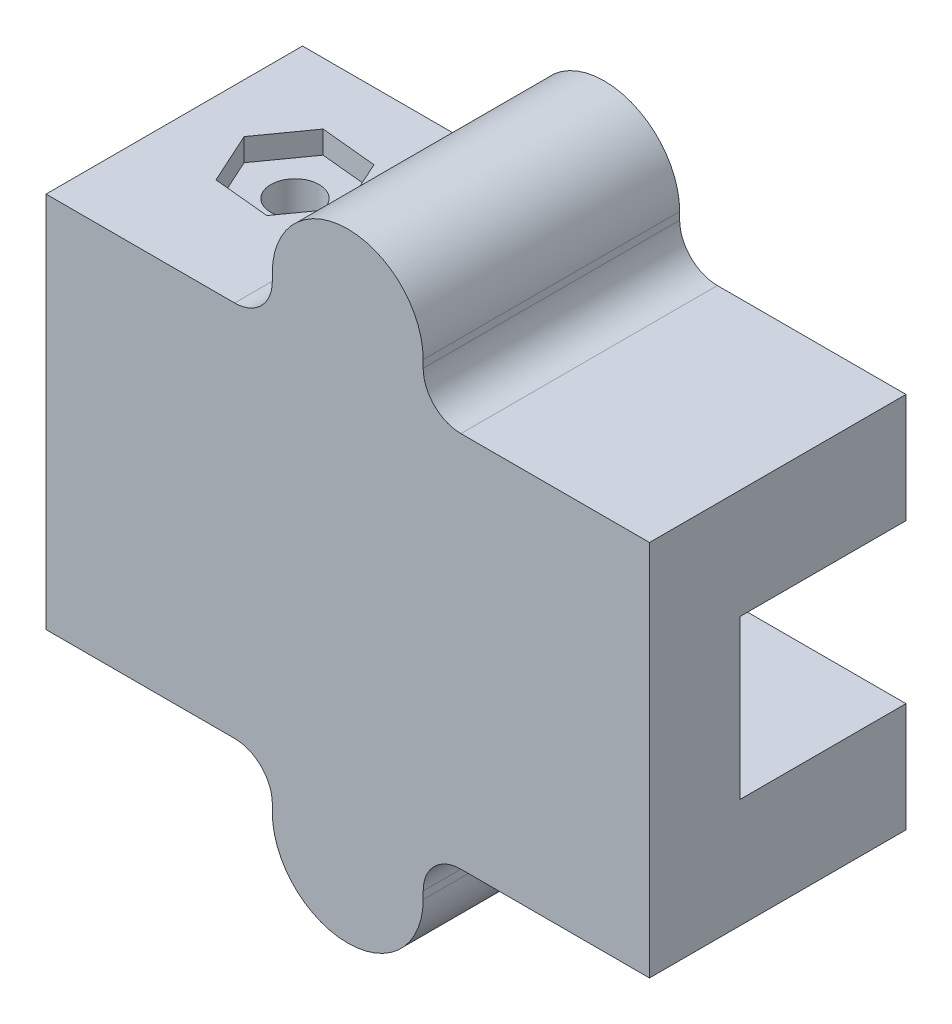
SolidWorks part; units mm, degrees
material "ABS"
ref_plane "Front Plane" through (0, 0, 0) normal (0, 0, 1) x (1, 0, 0)
ref_plane "Top Plane" through (0, 0, 0) normal (0, 1, 0) x (1, 0, 0)
ref_plane "Right Plane" through (0, 0, 0) normal (1, 0, 0) x (0, 0, -1)
sketch "Sketch1" plane through (0, 0, 0) normal (0, 0, 1) x (1, 0, 0)
  line L1 (0, 5.25) -> (0, -5.25) construction
  line L4 (-20, 12.5) -> (-7.5, 12.5)
  line L5 (20, -12.5) -> (20, 12.5)
  line L6 (-20, -12.5) -> (-7.5, -12.5)
  line L7 (-20, -12.5) -> (-20, 12.5)
  line L8 (-20, -5.25) -> (20, -5.25)
  line L9 (-20, -5.25) -> (20, -5.25) construction
  line L10 (-20, 5.25) -> (20, 5.25)
  line L11 (-20, 5.25) -> (20, 5.25) construction
  line L12 (-5, 15.5) -> (-5, 15)
  line L13 (5, 15.5) -> (5, 15)
  line L14 (7.5, 12.5) -> (20, 12.5)
  line L15 (-20, 12.5) -> (20, 12.5) construction
  line L17 (-20, 0) -> (20, 0) construction
  line L18 (7.5, -12.5) -> (20, -12.5)
  line L19 (-20, -12.5) -> (20, -12.5) construction
  line L20 (-5, -15) -> (-5, -15.5)
  line L21 (5, -15) -> (5, -15.5)
  circle A0 centre (0, 15.5) radius 2.4
  arc A1 (5, 15.5) -> (-5, 15.5) centre (0, 15.5) ccw
  arc A2 (5, 15) -> (7.5, 12.5) centre (7.5, 15) ccw
  arc A3 (-5, 15) -> (-7.5, 12.5) centre (-7.5, 15) cw
  arc A4 (5, -15) -> (7.5, -12.5) centre (7.5, -15) cw
  arc A5 (-5, -15) -> (-7.5, -12.5) centre (-7.5, -15) ccw
  circle A6 centre (0, -15.5) radius 2.4
  arc A7 (5, -15.5) -> (-5, -15.5) centre (0, -15.5) cw
  point P3 (0, 0)
  point P15 (5, 12.5)
  point P22 (-5, 12.5)
  dimension "D1" = 10.5
  dimension "D2" = 2.5
  dimension "D3" = 4.8
  dimension "D4" = 25
  dimension "D5" = 40
extrude "Boss-Extrude1" add sketch "Sketch1" along normal blind 11 contours L12 A3 L4 L7 L10 L5 L14 A2 L13 A1 A0 | A7 L21 A4 L18 L5 L8 L7 L6 A5 L20 A6 | A6 | A0 region at (0, 10.0051, 0) region at (0, -10.0051, 0) region at (0, 15.5, 0) region at (0, -15.5, 0)
extrude "Boss-Extrude2" add sketch "Sketch1<3>" along normal blind 6 from surface contours L12 A3 L4 L7 L10 L5 L14 A2 L13 A1 A0 | A6 | A7 L21 A4 L18 L5 L8 L7 L6 A5 L20 A6 | A0 | L10 L7 L8 L5 region at (0, 10.0051, 0) region at (0, 0, 0) region at (0, -10.0051, 0) region at (0, 15.5, 0) region at (0, -15.5, 0) starting at face at (0, 12.5464, 11)
sketch "Sketch1<3>" plane through (0, 0, 0) normal (0, 0, 1) x (1, 0, 0) same geometry as "Sketch1"
sketch "Sketch3" plane through (0, 0, 11) normal (0, 0, -1) x (-1, 0, 0)
  line L0 (-20, 0) -> (-14, 0) construction
  line L3 (-20, 5.25) -> (-20, -5.25) construction
  circle A0 centre (-14, 0) radius 4.25
  dimension "D1" = 8.5
  dimension "D2" = 6
extrude "Cut-Extrude1" cut sketch "Sketch3" against normal blind 5
sketch "Sketch4" plane through (0, -12.5, 0) normal (0, -1, 0) x (1, 0, 0)
  line L1 (-20, 17) -> (-20, 0) construction
  circle A0 centre (-13, 7.5) radius 1.6
  dimension "D1" = 3.2
  dimension "D2" = 7.5
  dimension "D3" = 7
extrude "Cut-Extrude2" cut sketch "Sketch4" against normal through all
sketch "Sketch5" plane through (0, 12.5, 0) normal (0, 1, 0) x (1, 0, 0)
  line L1 (-9.2649, -7.8639) -> (-10.8173, -4.4473)
  line L2 (-10.8173, -4.4473) -> (-14.5524, -4.0833)
  line L3 (-14.5524, -4.0833) -> (-16.7351, -7.1361)
  line L4 (-16.7351, -7.1361) -> (-15.1827, -10.5527)
  line L5 (-15.1827, -10.5527) -> (-11.4476, -10.9167)
  line L6 (-11.4476, -10.9167) -> (-9.2649, -7.8639)
  circle A0 centre (-13, -7.5) radius 3.25 construction
  dimension "D1" = 6.5
extrude "Cut-Extrude3" cut sketch "Sketch5" against normal blind 1.5
sketch "Sketch7" plane through (0, 0, 0) normal (0, 0, -1) x (-1, 0, 0)
  line L5 (-20, 0) -> (20, 0) construction
  line L18 (-5, 8.875) -> (5, 8.875) construction
  line L19 (-5, 11.475) -> (5, 11.475)
  line L20 (-5, 6.275) -> (5, 6.275)
  line L21 (-5, -8.875) -> (5, -8.875) construction
  line L22 (-5, -11.475) -> (5, -11.475)
  line L23 (-5, -6.275) -> (5, -6.275)
  line L24 (-20, 5.25) -> (-20, -5.25) construction
  line L25 (20, 5.25) -> (20, -5.25) construction
  arc A0 (-5, 11.475) -> (-5, 6.275) centre (-5, 8.875) ccw
  arc A1 (5, 6.275) -> (5, 11.475) centre (5, 8.875) ccw
  arc A2 (-5, -11.475) -> (-5, -6.275) centre (-5, -8.875) cw
  arc A3 (5, -6.275) -> (5, -11.475) centre (5, -8.875) cw
  point P8 (0, 8.875)
  point P15 (0, -8.875)
  dimension "D1" = 5.2
extrude "Cut-Extrude5" cut sketch "Sketch7" against normal blind 5.2
sketch "Sketch9" plane through (0, 0, 0) normal (0, 0, -1) x (-1, 0, 0)
  line L0 (20, 0) -> (-20, 0) construction
  line L1 (20, 5.25) -> (20, -5.25) construction
  line L2 (-20, 5.25) -> (-20, -5.25) construction
  circle A0 centre (0, -15.5) radius 2.4
  circle A1 centre (0, 15.5) radius 2.4
  dimension "D1" = 4.8
extrude "Cut-Extrude6" cut sketch "Sketch9" against normal blind 6
